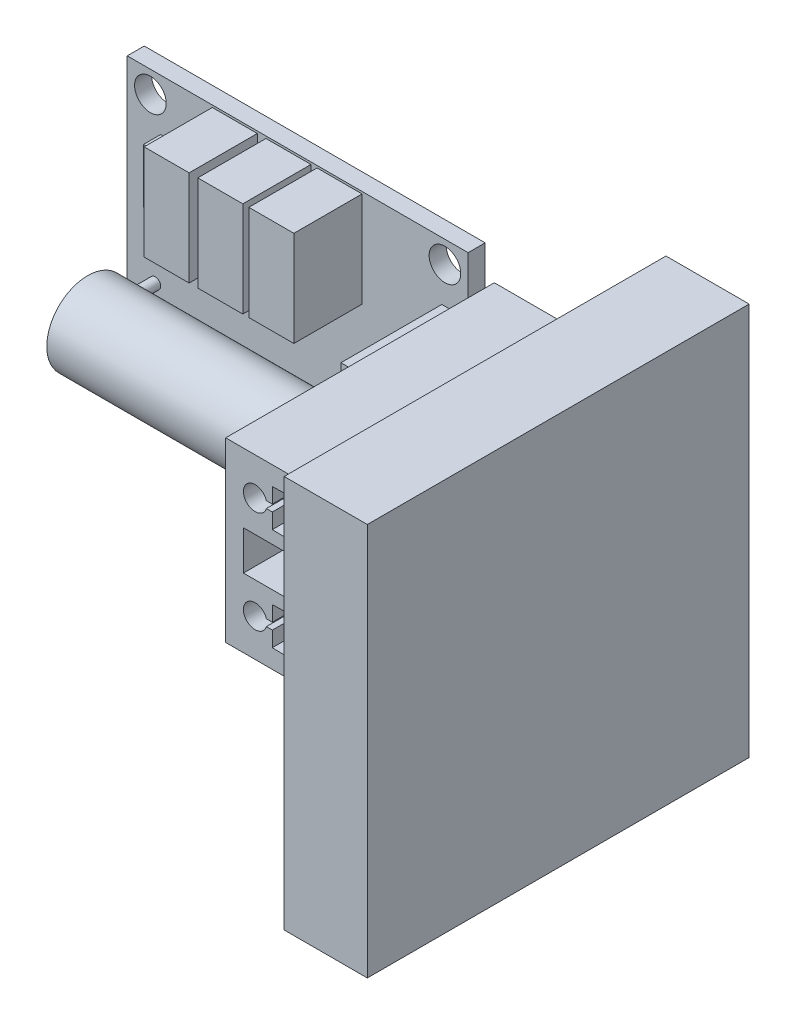
SolidWorks part; units mm, degrees
ref_plane "Front Plane" through (0, 0, 0) normal (0, 0, 1) x (1, 0, 0)
ref_plane "Top Plane" through (0, 0, 0) normal (0, 1, 0) x (1, 0, 0)
ref_plane "Right Plane" through (0, 0, 0) normal (1, 0, 0) x (0, 0, -1)
sketch "Sketch1" plane through (0, 0, 0) normal (0, 0, 1) x (1, 0, 0)
  line L1 (15.875, -11.049) -> (-15.875, -11.049)
  line L2 (15.875, -11.049) -> (15.875, 11.049)
  line L3 (15.875, 11.049) -> (-15.875, 11.049)
  line L4 (-15.875, -11.049) -> (-15.875, 11.049)
  line L5 (15.875, -11.049) -> (-15.875, 11.049) construction
  line L6 (15.875, 11.049) -> (-15.875, -11.049) construction
  point P0 (0, 0)
  point P6 (0, 0)
extrude "Boss-Extrude1" add sketch "Sketch1" against normal blind 1.5875
hole_wizard "#32 (0.116) Diameter Hole1" positions "Sketch3" profile "Sketch2" hole size "#32" standard "ANSI Inch"
sketch "Sketch3" plane through (0, 0, 0) normal (0, 0, 1) x (1, 0, 0)
  line L1 (13.716, -9.017) -> (-13.716, -9.017)
  line L2 (13.716, -9.017) -> (13.716, 9.017)
  line L3 (13.716, 9.017) -> (-13.716, 9.017)
  line L4 (-13.716, -9.017) -> (-13.716, 9.017)
  line L5 (13.716, -9.017) -> (-13.716, 9.017) construction
  line L6 (13.716, 9.017) -> (-13.716, -9.017) construction
  point P1 (-13.716, 9.017)
  point P266 (13.716, -9.017)
  point P267 (13.716, 9.017)
  point P268 (-13.716, -9.017)
sketch "Sketch2" plane through (-13.716, 9.017, 0) normal (1, 0, 0) x (0, -1, 0)
  line L0 (0, 0) -> (0, 26.2852)
  line L1 (0, 26.2852) -> (1.4732, 25.4)
  line L2 (1.4732, 25.4) -> (1.4732, 0)
  line L5 (1.4732, 0) -> (0, 0)
  line L10 (0, 26.2852) -> (-1.4732, 25.4) construction
  line L11 (0, -6.35) -> (0, 107.95) construction
  dimension "Hole Dia." = 2.9464
  dimension "Hole Depth" = 25.4
  dimension "Drill Angle" = 118
sketch "Sketch4" plane through (0, 0, 0) normal (0, 0, 1) x (1, 0, 0)
  line L0 (-2.9528, 10.8435) -> (1.2382, 10.8435)
  line L1 (9.5927, -9.7894) -> (-13.2673, -9.7894)
  line L2 (9.5927, -9.7894) -> (9.5927, -2.1694)
  line L3 (9.5927, -2.1694) -> (-13.2673, -2.1694)
  line L4 (-13.2673, -9.7894) -> (-13.2673, -2.1694)
  line L5 (9.5927, -9.7894) -> (-13.2673, -2.1694) construction
  line L6 (9.5927, -2.1694) -> (-13.2673, -9.7894) construction
  line L7 (-7.9494, 10.8458) -> (-3.7584, 10.8458)
  line L8 (-7.9494, 10.8458) -> (-7.9494, 1.9558)
  line L9 (-7.9494, 1.9558) -> (-3.7584, 1.9558)
  line L10 (-3.7584, 10.8458) -> (-3.7584, 1.9558)
  line L11 (-7.9494, 10.8458) -> (-3.7584, 1.9558) construction
  line L12 (-7.9494, 1.9558) -> (-3.7584, 10.8458) construction
  line L13 (-2.9528, 10.8435) -> (-2.9528, 1.9535)
  line L14 (-2.9528, 1.9535) -> (1.2382, 1.9535)
  line L15 (1.2382, 10.8435) -> (1.2382, 1.9535)
  line L16 (-2.9528, 10.8435) -> (1.2382, 1.9535) construction
  line L17 (-2.9528, 1.9535) -> (1.2382, 10.8435) construction
  line L18 (1.8053, 10.8458) -> (5.9963, 10.8458)
  line L19 (1.8053, 10.8458) -> (1.8053, 1.9558)
  line L20 (1.8053, 1.9558) -> (5.9963, 1.9558)
  line L21 (5.9963, 10.8458) -> (5.9963, 1.9558)
  line L22 (1.8053, 10.8458) -> (5.9963, 1.9558) construction
  line L23 (1.8053, 1.9558) -> (5.9963, 10.8458) construction
  line L26 (-12.7645, 6.2555) -> (-10.2982, 6.2555)
  line L27 (-12.7645, 6.2555) -> (-12.7645, 1.1896)
  line L28 (-12.7645, 1.1896) -> (-10.2982, 1.1896)
  line L29 (-10.2982, 6.2555) -> (-10.2982, 1.1896)
  line L30 (-12.7645, 6.2555) -> (-10.2982, 1.1896) construction
  line L31 (-12.7645, 1.1896) -> (-10.2982, 6.2555) construction
  circle A0 centre (-13.2673, -5.9794) radius 0.508
  circle A1 centre (9.5927, -5.9794) radius 0.508
  point P0 (-1.8373, -5.9794)
  point P5 (-5.8539, 6.4008)
  point P10 (-0.8573, 6.3985)
  point P15 (3.9008, 6.4008)
  point P22 (-11.5313, 3.7225)
extrude "Boss-Extrude2" add sketch "Sketch4" along normal blind 6.35 contours L10 L7 L8 L9 | L15 L0 L13 L14 | L21 L18 L19 L20 region at (-0.8573, 6.3985, 0) region at (-5.8539, 6.4008, 0) region at (3.9008, 6.4008, 0)
extrude "Boss-Extrude3" add sketch "Sketch4<3>" along normal blind 1.5875 contours L27 L28 L29 L26
sketch "Sketch4<3>" plane through (0, 0, 0) normal (0, 0, 1) x (1, 0, 0) same geometry as "Sketch4"
extrude "Boss-Extrude4" add sketch "Sketch4<4>" along normal blind 6.35 contours L4 A0 | L4 A0 | L2 A1 | L2 A1 region at (9.3771, -5.9794, 0) region at (9.8083, -5.9794, 0) region at (-13.4829, -5.9794, 0) region at (-13.0517, -5.9794, 0)
sketch "Sketch4<4>" plane through (0, 0, 0) normal (0, 0, 1) x (1, 0, 0) same geometry as "Sketch4"
sketch "Sketch5" plane through (0, 0, 0) normal (1, 0, 0) x (0, 0, -1)
  line L0 (-6.35, -5.4714) -> (-6.35, -6.4874) construction
  circle A0 centre (-6.35, -5.9794) radius 3.81
extrude "Boss-Extrude5" add sketch "Sketch5" along normal blind 9.398 and the other way blind 13.208
sketch "Sketch6" plane through (0, 0, 0) normal (0, 0, 1) x (1, 0, 0)
  line L1 (13.4257, -5.645) -> (16.7277, -5.645)
  line L2 (13.4257, -5.645) -> (13.4257, 5.645)
  line L3 (13.4257, 5.645) -> (16.7277, 5.645)
  line L4 (16.7277, -5.645) -> (16.7277, 5.645)
  line L5 (13.4257, -5.645) -> (16.7277, 5.645) construction
  line L6 (13.4257, 5.645) -> (16.7277, -5.645) construction
  point P0 (15.0767, 0)
extrude "Boss-Extrude6" add sketch "Sketch6" along normal blind 9.398
sketch "Sketch8" plane through (16.7277, 0, 0) normal (1, 0, 0) x (0, 0, -1)
  line L0 (1.5875, -11.049) -> (1.5875, 11.049) construction
  line L1 (1.5875, -8.255) -> (-23.4315, -8.255)
  line L3 (1.5875, 8.255) -> (-23.4315, 8.255)
  line L4 (-23.4315, -8.255) -> (-23.4315, 8.255)
  line L5 (1.5875, 0) -> (-23.4315, 8.255) construction
  line L6 (1.5875, 0) -> (-23.4315, -8.255) construction
  line L7 (1.5875, 8.255) -> (1.5875, -8.255)
  point P0 (1.5875, 0)
extrude "Boss-Extrude7" add sketch "Sketch8" along normal blind 15.875
sketch "Sketch9" plane through (0, 0, 23.4315) normal (0, 0, 1) x (1, 0, 0)
  line L0 (32.6027, 8.255) -> (32.6027, -8.255) construction
  line L1 (18.3787, 0) -> (18.3787, 1.8288)
  line L2 (32.6027, 4.7625) -> (32.6027, 6.731)
  line L3 (21.0711, 5.08) -> (21.0711, 6.5024)
  line L4 (32.6027, 4.7625) -> (32.6027, 2.794)
  line L6 (32.6027, 1.8288) -> (18.3787, 1.8288)
  line L7 (18.3787, 0) -> (18.3787, -1.8288)
  line L8 (21.0711, -3.0226) -> (32.6027, -2.794)
  line L9 (21.0711, 3.0226) -> (32.6027, 2.794)
  line L10 (21.0711, -5.08) -> (21.0711, -6.5024)
  line L11 (32.6027, -4.7625) -> (32.6027, -6.731)
  line L12 (21.0711, -6.5024) -> (32.6027, -6.731)
  line L13 (32.6027, -4.7625) -> (32.6027, -2.794)
  line L14 (21.0711, 6.5024) -> (32.6027, 6.731)
  line L15 (32.6027, -1.8288) -> (18.3787, -1.8288)
  line L16 (32.6027, -1.8288) -> (32.6027, 1.8288)
  line L17 (18.3787, 0) -> (18.3787, -1.8288)
  line L18 (18.3787, 0) -> (18.3787, 1.8288)
  line L19 (21.0711, 4.445) -> (21.0711, 3.0226)
  line L20 (32.6027, 8.255) -> (16.7277, 8.255) construction
  line L25 (21.0711, -4.445) -> (21.0711, -3.0226)
  line L26 (21.0711, -5.08) -> (20.5159, -5.08)
  line L28 (21.0711, -4.445) -> (20.5159, -4.445)
  line L32 (21.0711, 4.445) -> (20.5159, 4.445)
  line L34 (21.0711, 5.08) -> (20.5159, 5.08)
  arc A1 (20.5159, -4.445) -> (20.5159, -5.08) centre (19.4709, -4.7625) ccw
  arc A2 (20.5159, 5.08) -> (20.5159, 4.445) centre (19.4709, 4.7625) ccw
  point P3 (20.8171, -4.7625)
  point P19 (24.6652, 8.255)
  point P40 (20.8171, 4.7625)
  line M40 (32.6027, -8.255) -> (32.6027, 8.255)
extrude "Cut-Extrude1" cut sketch "Sketch9" against normal through all contours L15 L6 L1 L7 M40 | L14 L2 L4 L9 L19 L32 A2 L34 L3 | L8 L13 L11 L12 L10 L26 A1 L28 L25 region at (25.4907, 0, 23.4315)
sketch "Sketch10" plane through (32.6027, 0, 0) normal (1, 0, 0) x (0, 0, -1)
  line L1 (1.7014, -18.2904) -> (-33.8614, -18.2904)
  line L2 (1.7014, -18.2904) -> (1.7014, 18.2904)
  line L3 (1.7014, 18.2904) -> (-33.8614, 18.2904)
  line L4 (-33.8614, -18.2904) -> (-33.8614, 18.2904)
  line L5 (1.7014, -18.2904) -> (-33.8614, 18.2904) construction
  line L6 (1.7014, 18.2904) -> (-33.8614, -18.2904) construction
  point P0 (-16.08, 0)
extrude "Boss-Extrude8" add sketch "Sketch10" along normal blind 7.747
